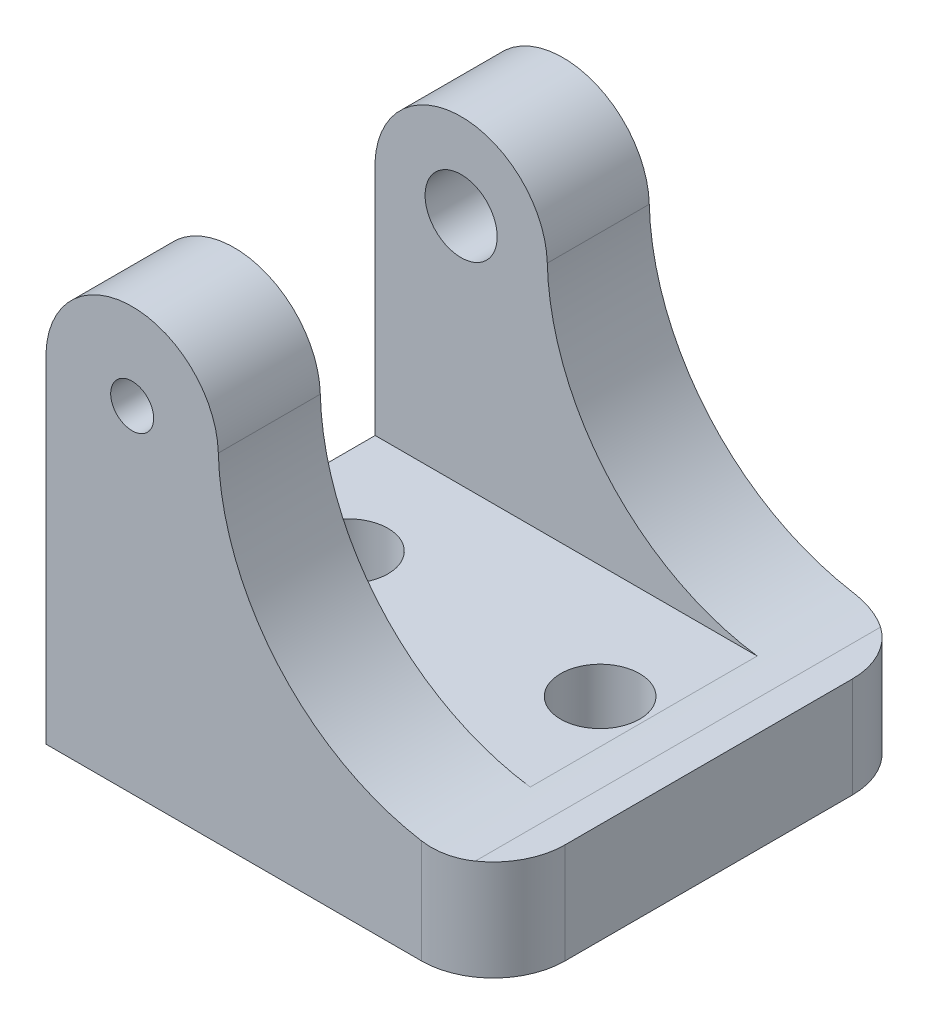
SolidWorks part; units mm, degrees
material "1060 Alloy"
ref_plane "Front Plane" through (0, 0, 0) normal (0, 0, 1) x (1, 0, 0)
ref_plane "Top Plane" through (0, 0, 0) normal (0, 1, 0) x (1, 0, 0)
ref_plane "Right Plane" through (0, 0, 0) normal (1, 0, 0) x (0, 0, -1)
sketch "Sketch1" plane through (0, 0, 0) normal (0, 0, 1) x (1, 0, 0)
  line L0 (-19.7612, 0) -> (19.7612, 0)
  line L1 (-19.7612, 0) -> (-19.7612, 29.1338)
  line L2 (17.0372, 8.89) -> (19.7612, 8.89)
  line L3 (19.7612, 8.89) -> (19.7612, 0)
  arc A0 (-19.7612, 29.1338) -> (-4.5451, 29.9052) centre (-12.1624, 29.7024) cw
  arc A1 (-4.5451, 29.9052) -> (17.0372, 8.89) centre (17.0372, 30.48) ccw
  point P6 (0, 0)
  point P10 (-12.5483, 37.3126)
  dimension "D4" = 7.62
  dimension "D5" = 21.59
  dimension "D1" = 39.5224
  dimension "D2" = 29.1338
  dimension "D3" = 8.89
  dimension "D6" = 37.3126
extrude "Boss-Extrude1" add sketch "Sketch1" against normal blind 38.1
sketch "Sketch3" plane through (-19.7612, 0, 0) normal (-1, 0, 0) x (0, 0, 1)
  line L0 (0, 37.3224) -> (-38.1, 37.3224) construction
  line L1 (-38.1, 37.3224) -> (-38.1, 29.1338) construction
  line L2 (0, -20.5263) -> (0, 20.5263) construction
  line L3 (-29.083, 37.3224) -> (-9.017, 37.3224)
  line L4 (-9.017, 37.3224) -> (-9.017, 9.103)
  line L5 (-9.017, 9.103) -> (-29.083, 9.103)
  line L6 (-29.083, 9.103) -> (-29.083, 37.3224)
  point P0 (-29.083, 37.3224)
  point P1 (-9.017, 37.3224)
  dimension "D1" = 9.017
  dimension "D2" = 9.017
  dimension "D3" = 28.2194
extrude "Cut-Extrude1" cut sketch "Sketch3" against normal through all both and the other way through all
sketch "Sketch6" plane through (0, 0, 0) normal (0, 0, 1) x (1, 0, 0)
  point P0 (-12.1624, 29.7024)
hole_wizard "#10-24 Tapped Hole1" positions "Sketch8" profile "Sketch7" tap size "#10-24" standard "ANSI Inch"
sketch "Sketch8" plane through (0, 0, 0) normal (0, 0, 1) x (1, 0, 0)
  point P0 (-12.1624, 29.7024)
sketch "Sketch7" plane through (-12.1624, 29.7024, 0) normal (1, 0, 0) x (0, -1, 0)
  line L0 (0, 0) -> (0, 14.0948)
  line L1 (0, 14.0948) -> (1.8986, 12.954)
  line L2 (1.8986, 12.954) -> (1.8986, 0)
  line L5 (1.8986, 0) -> (0, 0)
  line L10 (0, 14.0948) -> (-1.8986, 12.954) construction
  line L11 (0, -6.35) -> (0, 107.95) construction
  dimension "Tap Drill Dia." = 3.7973
  dimension "Tap Drill Depth" = 12.954
  dimension "Drill Angle" = 118
cosmetic thread "Hole Thread1" parameters "D1"=9.017, "D2"=4.826
sketch "Sketch9" plane through (0, 0, -38.1) normal (0, 0, -1) x (-1, 0, 0)
  point P0 (12.1624, 29.7024)
hole_wizard "CBORE for 1/4 Socket Shoulder Screw1" positions "Sketch11" profile "Sketch12" counterbore size "1/4" standard "ANSI Inch" end condition up to next
sketch "Sketch11" plane through (0, 0, -38.1) normal (0, 0, -1) x (-1, 0, 0)
  point P0 (12.1624, 29.7024)
sketch "Sketch12" plane through (-12.1624, 29.7024, -38.1) normal (1, 0, 0) x (0, 1, 0)
  line L0 (0, 0) -> (0, 9.017)
  line L1 (0, 9.017) -> (3.1877, 9.017)
  line L3 (3.1877, 9.017) -> (3.1877, 3.8862)
  line L4 (3.1877, 3.8862) -> (5.1308, 3.8862)
  line L5 (5.1308, 3.8862) -> (5.1308, 0)
  line L7 (5.1308, 0) -> (0, 0)
  line L11 (0, -6.35) -> (0, 107.95) construction
  dimension "Thru Hole Dia." = 6.3754
  dimension "Thru Hole Depth" = 9.017
  dimension "C'Bore Dia." = 10.2616
  dimension "C'Bore Depth" = 3.8862
sketch "Sketch13" plane through (0, 0, 0) normal (0, -1, 0) x (1, 0, 0)
  line L0 (-19.7612, -38.1) -> (-19.7612, 0) construction
  line L1 (19.7612, -38.1) -> (19.7612, 0) construction
  line L2 (-19.7612, -19.05) -> (19.7612, -19.05) construction
  circle A0 centre (-12.0904, -19.05) radius 3.4925
  circle A1 centre (10.16, -19.05) radius 3.4925
  dimension "D1" = 6.985
  dimension "D2" = 22.2504
  dimension "D3" = 7.6708
extrude "Cut-Extrude2" cut sketch "Sketch13" against normal through all
fillet "Fillet1" radius 6.35 2 edges at (19.7612, 4.445, -38.1) (19.7612, 4.445, 0)
